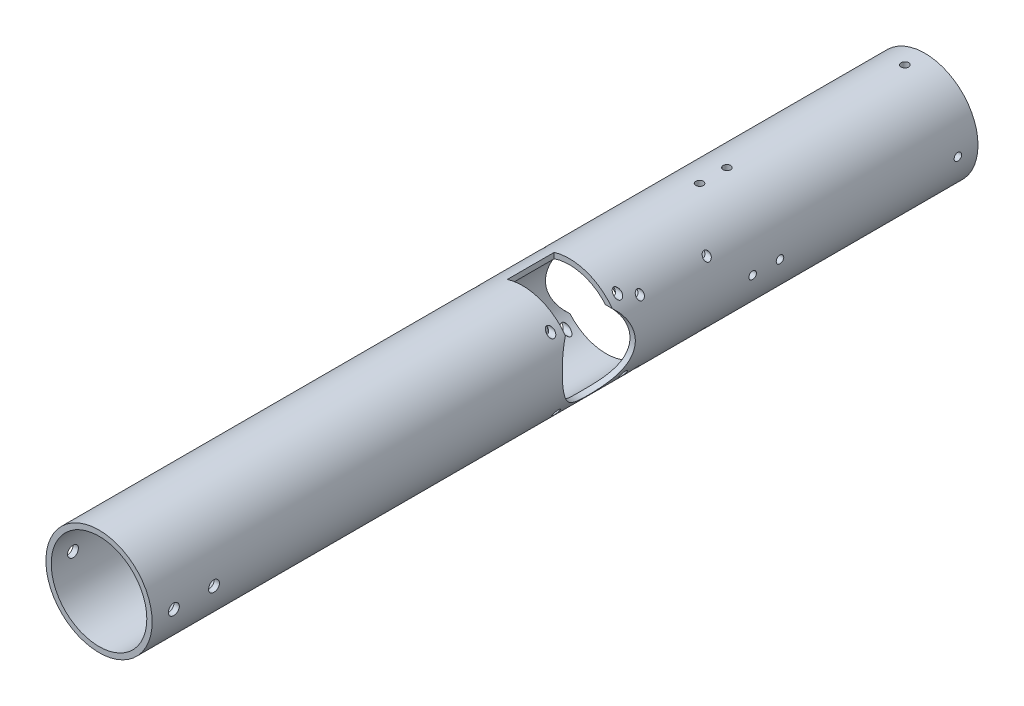
SolidWorks part; units mm, degrees
material "6061 Alloy"
ref_plane "Front Plane" through (0, 0, 0) normal (0, 0, 1) x (1, 0, 0)
ref_plane "Top Plane" through (0, 0, 0) normal (0, 1, 0) x (1, 0, 0)
ref_plane "Right Plane" through (0, 0, 0) normal (1, 0, 0) x (0, 0, -1)
sketch "Sketch1" plane through (0, 0, 0) normal (0, 0, 1) x (1, 0, 0)
  circle A0 centre (0, 0) radius 31.75
  circle A1 centre (0, 0) radius 28.575
  dimension "D1" = 63.5
  dimension "D2" = 57.15
extrude "Boss-Extrude1" add sketch "Sketch1" along normal blind 125 and the other way blind 250 contours A1 | A0
sketch "Sketch2" plane through (0, 0, 0) normal (1, 0, 0) x (0, 0, -1)
  circle A2 centre (73.488, -2) radius 21.75
  dimension "D1" = 43.5
  dimension "D2" = 73.488
  dimension "D3" = 2
extrude "Cut-Extrude1" cut sketch "Sketch2" against normal through all
sketch "Sketch3" plane through (0, 0, 0) normal (1, 0, 0) x (0, 0, -1)
  circle A1 centre (23.45, 2) radius 21.75
  dimension "D1" = 23.45
  dimension "D2" = 43.5
  dimension "D3" = 2
extrude "Cut-Extrude2" cut sketch "Sketch3" along normal through all
sketch "Sketch5" plane through (0, 0, 0) normal (1, 0, 0) x (0, 0, -1)
  line L1 (87.488, -12.75) -> (59.488, -12.75)
  line L2 (87.488, -12.75) -> (87.488, -34.75)
  line L3 (87.488, -34.75) -> (59.488, -34.75)
  line L4 (59.488, -12.75) -> (59.488, -34.75)
  line L5 (87.488, -12.75) -> (59.488, -34.75) construction
  line L6 (87.488, -34.75) -> (59.488, -12.75) construction
  circle A0 centre (73.488, -2) radius 21.75 construction
  circle A1 centre (73.488, -2) radius 21.75 construction
  circle A2 centre (73.488, -2) radius 21.75 construction
  point P0 (73.488, -23.75)
  dimension "D1" = 28
  dimension "D2" = 22
extrude "Cut-Extrude4" cut sketch "Sketch5" against normal through all from offset 9
sketch "Sketch6" plane through (0, 0, 0) normal (1, 0, 0) x (0, 0, -1)
  line L1 (9.45, 34.75) -> (37.45, 34.75)
  line L2 (9.45, 34.75) -> (9.45, 12.75)
  line L3 (9.45, 12.75) -> (37.45, 12.75)
  line L4 (37.45, 34.75) -> (37.45, 12.75)
  line L5 (9.45, 34.75) -> (37.45, 12.75) construction
  line L6 (9.45, 12.75) -> (37.45, 34.75) construction
  circle A0 centre (23.45, 2) radius 21.75 construction
  circle A1 centre (23.45, 2) radius 21.75 construction
  circle A2 centre (23.45, 2) radius 21.75 construction
  point P0 (23.45, 23.75)
  dimension "D1" = 28
  dimension "D2" = 22
extrude "Cut-Extrude5" cut sketch "Sketch6" along normal through all from offset 9 offset against normal yes
sketch "Sketch10" plane through (0, 0, 0) normal (1, 0, 0) x (0, 0, -1)
  line L1 (113.488, 38) -> (33.488, 38)
  line L2 (113.488, 38) -> (113.488, -42)
  line L3 (113.488, -42) -> (33.488, -42)
  line L4 (33.488, 38) -> (33.488, -42)
  line L5 (113.488, 38) -> (33.488, -42) construction
  line L6 (113.488, -42) -> (33.488, 38) construction
  point P0 (73.488, -2)
  dimension "D1" = 80
  dimension "D2" = 80
sketch "Sketch11" plane through (0, 0, 0) normal (1, 0, 0) x (0, 0, -1)
  line L0 (113.488, 38) -> (33.488, -42) construction
  line L1 (113.488, -42) -> (33.488, 38) construction
  line L2 (51.738, -2) -> (95.238, -2) construction
  line L3 (53.488, 18) -> (53.488, -22) construction
  circle A0 centre (93.488, 18) radius 2
  circle A1 centre (53.488, 18) radius 2
  circle A2 centre (53.488, -22) radius 2
  circle A3 centre (93.488, -22) radius 2
  arc A4 (87.488, -18.6452) -> (59.488, -18.6452) centre (73.488, -2) ccw construction
  arc A5 (87.488, -18.6452) -> (59.488, -18.6452) centre (73.488, -2) ccw construction
  point P18 (53.488, -2)
  dimension "D5" = 4
  dimension "D1" = 40
extrude "Cut-Extrude8" cut sketch "Sketch11" against normal through all both and the other way through all
sketch "Sketch12" plane through (0, 0, 0) normal (1, 0, 0) x (0, 0, -1)
  line L0 (-125, 31.75) -> (-125, -31.75) construction
  circle A0 centre (-112, 0) radius 3.25
  circle A1 centre (-88, 0) radius 3.25
  dimension "D2" = 6.5
  dimension "D3" = 24
  dimension "D4" = 13
extrude "Cut-Extrude10" cut sketch "Sketch12" against normal through all both and the other way through all
sketch "Sketch13" plane through (0, 0, 0) normal (0, 1, 0) x (1, 0, 0)
  line L0 (0, -34.925) -> (0, 34.925) construction
  line L1 (28.575, 250) -> (-28.575, 250) construction
  line L2 (0, 250) -> (0, -125) construction
  circle A0 centre (0, 238) radius 2.25
  circle A1 centre (0, 205.9) radius 2.25 construction
  dimension "D2" = 4.5
  dimension "D3" = 32.1
  dimension "D1" = 12
extrude "Cut-Extrude11" cut sketch "Sketch13" against normal through all both and the other way through all
sketch "Sketch14" plane through (0, 0, 0) normal (1, 0, 0) x (0, 0, -1)
  line L0 (3.45, -18) -> (3.45, 22) construction
  line L1 (-1.55, 27) -> (48.45, 27) construction
  line L2 (-1.55, 27) -> (-1.55, -23) construction
  line L3 (-1.55, -23) -> (48.45, -23) construction
  line L4 (48.45, 27) -> (48.45, -23) construction
  line L5 (-1.55, 27) -> (48.45, -23) construction
  line L6 (-1.55, -23) -> (48.45, 27) construction
  circle A0 centre (3.45, 22) radius 2
  circle A1 centre (43.45, 22) radius 2
  circle A2 centre (43.45, -18) radius 2
  circle A3 centre (3.45, -18) radius 2
  point P0 (23.45, 2)
  point P14 (3.45, 2)
  dimension "D5" = 4
  dimension "D1" = 40
  dimension "D2" = 50
sketch "Sketch15" plane through (0, 0, 0) normal (1, 0, 0) x (0, 0, -1)
  circle A0 centre (3.45, 22) radius 2
  circle A1 centre (43.45, 22) radius 2
  circle A2 centre (43.45, -18) radius 2
  circle A3 centre (3.45, -18) radius 2
  dimension "D1" = 4
extrude "Cut-Extrude12" cut sketch "Sketch15" against normal through all and the other way through all
hole_wizard "M4 Clearance Hole1" positions "Sketch18" profile "Sketch19" hole size "M4" standard "ANSI Metric"
sketch "Sketch18" plane through (0, 0, 0) normal (1, 0, 0) x (0, 0, -1)
  circle A0 centre (3.45, 22) radius 2 construction
  circle A1 centre (43.45, 22) radius 2 construction
  circle A2 centre (3.45, -18) radius 2 construction
  circle A3 centre (43.45, -18) radius 2 construction
  point P0 (3.45, 22)
  point P2 (43.45, 22)
  point P4 (3.45, -18)
  point P6 (43.45, -18)
  point P20 (93.488, 18)
  point P23 (53.488, 18)
  point P26 (93.488, -22)
  point P29 (53.488, -22)
sketch "Sketch19" plane through (0, 22, -3.45) normal (0, 1, 0) x (0, 0, 1)
  line L0 (0, 0) -> (0, 31.75)
  line L1 (0, 31.75) -> (2.25, 31.75)
  line L2 (2.25, 31.75) -> (2.25, 0)
  line L5 (2.25, 0) -> (0, 0)
  line L11 (0, -6.35) -> (0, 107.95) construction
  dimension "Thru Hole Dia." = 4.5
  dimension "Thru Hole Depth" = 31.75
mirror "Mirror1" about plane through (0, 0, 0) normal (1, 0, 0) of "M4 Clearance Hole1"
sketch "Sketch21" plane through (0, 0, -250) normal (0, 0, -1) x (-1, 0, 0)
  circle A0 centre (0, 0) radius 30
  dimension "D1" = 60
extrude "Cut-Extrude14" cut sketch "Sketch21" against normal blind 7
pattern_circular "CirPattern1" count 2 every 90 about axis through (0, 0, -250) along (0, 0, 1) of "Cut-Extrude11"
sketch "Sketch22" plane through (0, 0, 0) normal (1, 0, 0) x (0, 0, -1)
  circle A0 centre (221.65, 0) radius 2.25 construction
  circle A1 centre (131.65, 0) radius 2.25
  circle A2 centre (115.3, 0) radius 2.25
  circle A3 centre (238, 0) radius 2.25 construction
  circle A4 centre (238, 0) radius 2.25 construction
  dimension "D1" = 16.35
  dimension "D2" = 106.35
  dimension "D3" = 122.7
extrude "Cut-Extrude15" cut sketch "Sketch22" along normal through all
pattern_circular "CirPattern2" count 4 over 360 about axis through (0, 0, -250) along (0, 0, 1) of "Cut-Extrude15"
sketch "Sketch23" plane through (0, 0, -243) normal (0, 0, -1) x (-1, 0, 0)
  circle A0 centre (0, 0) radius 28.575 construction
  circle A1 centre (0, 0) radius 30
  circle A2 centre (0, 0) radius 30
  circle A3 centre (0, 0) radius 28.575
  dimension "D1" = 0
extrude "Boss-Extrude2" add sketch "Sketch23" along normal up to surface (7 mm away) up to face at (-30, 0, -250)
ref_plane "Plane1" through (0, 0, 75) normal (0, 0, 1) x (1, 0, 0)
split "Split1" trim tools "Plane1" bodies to split 124 resulting bodies 125 126
move or copy body "Body-Move/Copy1" bodies to move or copy 125 copy no translate (0, 0, 118.65) parameters "D1"=0, "D2"=0, "D3"=118.65
sketch "Sketch24" plane through (0, 0, 75) normal (0, 0, 1) x (1, 0, 0)
  circle A0 centre (0, 0) radius 28.575 construction
  circle A1 centre (0, 0) radius 31.75
  circle A2 centre (0, 0) radius 31.75
  circle A3 centre (0, 0) radius 28.575
  dimension "D1" = 0
extrude "Boss-Extrude3" add sketch "Sketch24" along normal up to surface (118.65 mm away) up to face at (31.75, 0, 193.65)
